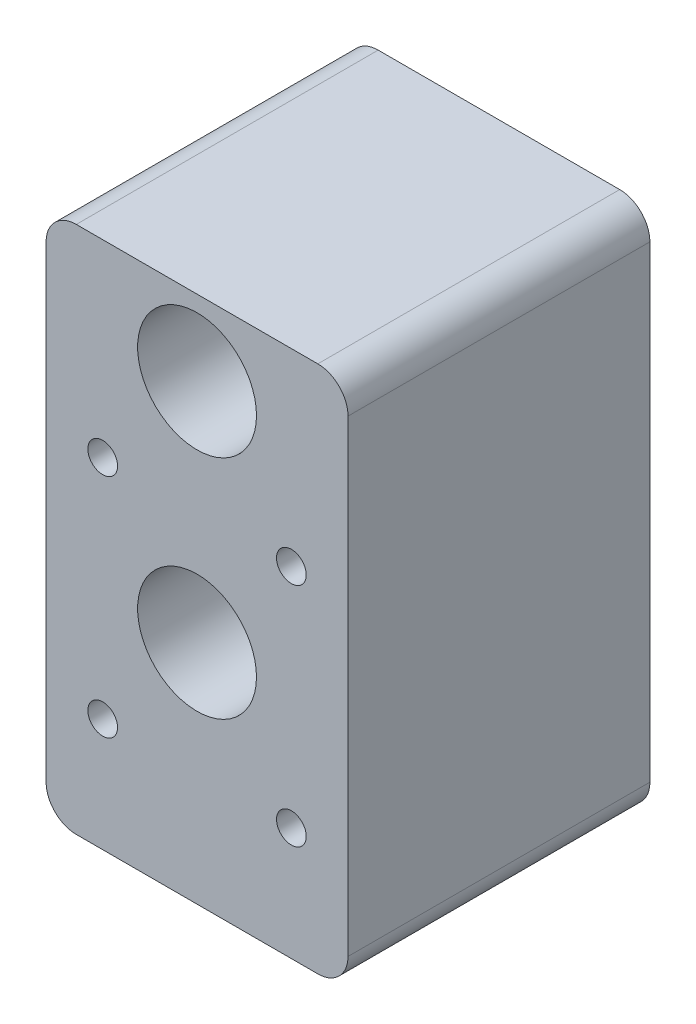
SolidWorks part; units mm, degrees
ref_plane "Front Plane" through (0, 0, 0) normal (0, 0, 1) x (1, 0, 0)
ref_plane "Top Plane" through (0, 0, 0) normal (0, 1, 0) x (1, 0, 0)
ref_plane "Right Plane" through (0, 0, 0) normal (1, 0, 0) x (0, 0, -1)
sketch "Sketch1" plane through (0, 0, 0) normal (0, 0, 1) x (1, 0, 0)
  line L0 (0, 0) -> (0, 31.75) construction
  line L6 (-12.7, 76.2) -> (12.7, 76.2)
  line L7 (-12.7, 76.2) -> (-12.7, 31.75)
  line L8 (-12.7, 31.75) -> (12.7, 31.75)
  line L9 (12.7, 76.2) -> (12.7, 31.75)
  line L10 (5, 76.2) -> (10, 76.2) construction
  dimension "D1" = 44.45
  dimension "D2" = 25.4
extrude "Boss-Extrude1" add sketch "Sketch1" along normal blind 25.4
sketch "Sketch2" plane through (0, 0, 25.4) normal (0, 0, 1) x (1, 0, 0)
  circle A0 centre (0, 50.8) radius 2.75
  circle A1 centre (0, 69.85) radius 2.75
  point P6 (0, 0)
  point P7 (0, 0)
  point P8 (0, 0)
  point P9 (0, 63.5)
  point P11 (0, 44.45)
  dimension "D1" = 5.5
extrude "Cut-Extrude1" cut sketch "Sketch2" against normal through all
sketch "Sketch3" plane through (0, 0, 25.4) normal (0, 0, 1) x (1, 0, 0)
  circle A0 centre (0, 50.8) radius 5
  circle A1 centre (0, 69.85) radius 5
  dimension "D1" = 10
extrude "Cut-Extrude2" cut sketch "Sketch3" against normal offset from surface (22.225 mm away) 3.175 up to face at (2.75, 50.8, 0)
sketch "Sketch5" plane through (0, 0, 25.4) normal (0, 0, 1) x (1, 0, 0)
  circle A0 centre (7.9375, 41.275) radius 1.25
  circle A1 centre (-7.9375, 41.275) radius 1.25
  circle A2 centre (-7.9375, 60.325) radius 1.25
  circle A3 centre (7.9375, 60.325) radius 1.25
  dimension "D1" = 2.5
extrude "Cut-Extrude3" cut sketch "Sketch5" against normal through all
fillet "Fillet1" radius 2.54 4 edges at (-12.7, 31.75, 12.7) (12.7, 31.75, 12.7) (-12.7, 76.2, 12.7) (12.7, 76.2, 12.7)
